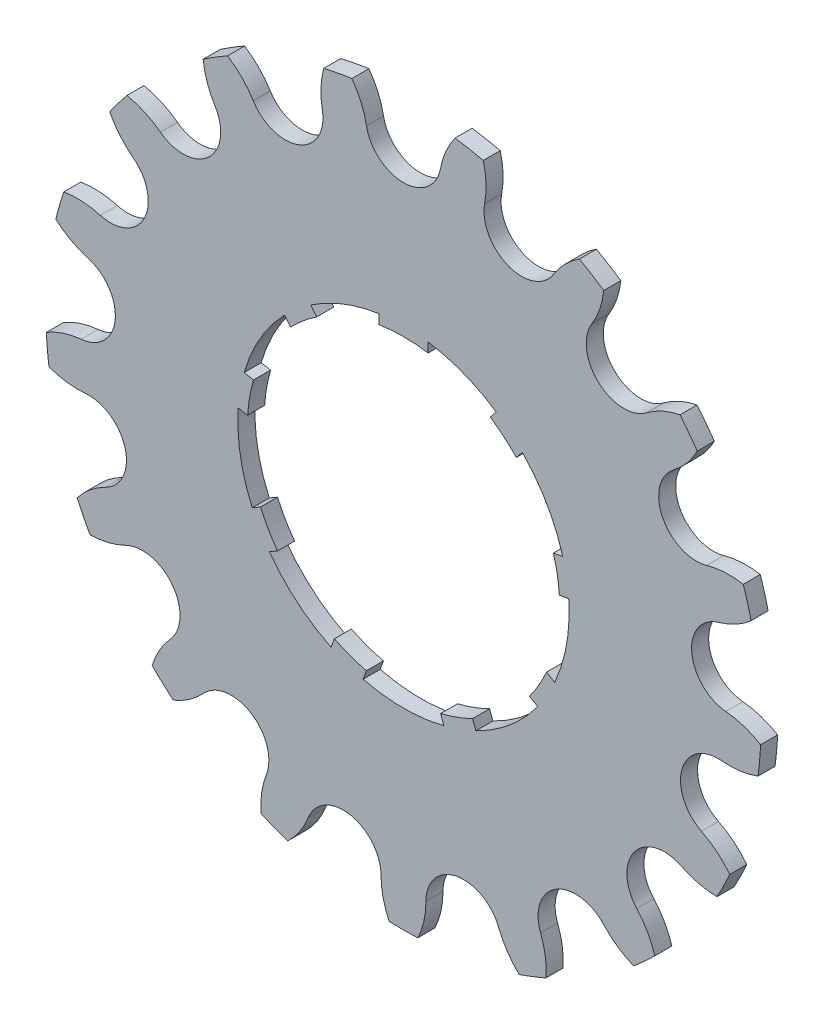
SolidWorks part; units mm, degrees
ref_plane "Alzado" through (0, 0, 0) normal (0, 0, 1) x (1, 0, 0)
ref_plane "Planta" through (0, 0, 0) normal (0, 1, 0) x (1, 0, 0)
ref_plane "Vista lateral" through (0, 0, 0) normal (1, 0, 0) x (0, 0, -1)
sketch "Sk_Disco" plane through (0, 0, 0) normal (0, 0, 1) x (1, 0, 0)
  line L0 (2.6, 17.3058) -> (2.6, 16.2939)
  line L1 (-2.6, 16.2939) -> (-2.6, 17.3058)
  line L2 (-9.8102, 14.4917) -> (-9.1638, 13.7213)
  line L3 (-11.9216, 11.4073) -> (-12.568, 12.1777)
  line L4 (-16.8302, 4.7954) -> (-15.8398, 4.6207)
  line L5 (-16.4649, 1.0754) -> (-17.4553, 1.2501)
  line L6 (-15.9751, -7.1447) -> (-15.1041, -6.6419)
  line L7 (-13.3041, -9.7596) -> (-14.1751, -10.2624)
  line L8 (-7.6451, -15.7418) -> (-7.3011, -14.7968)
  line L9 (-3.9182, -16.028) -> (-4.2622, -16.973)
  line L10 (4.2622, -16.973) -> (3.9182, -16.028)
  line L11 (7.3011, -14.7968) -> (7.6451, -15.7418)
  line L12 (14.1751, -10.2624) -> (13.3041, -9.7596)
  line L13 (15.1041, -6.6419) -> (15.9751, -7.1447)
  line L14 (17.4553, 1.2501) -> (16.4649, 1.0754)
  line L15 (15.8398, 4.6207) -> (16.8302, 4.7954)
  line L16 (12.568, 12.1777) -> (11.9216, 11.4073)
  line L17 (9.1638, 13.7213) -> (9.8102, 14.4917)
  circle A0 centre (0, 0) radius 37.7795
  arc A1 (2.6, 16.2939) -> (-2.6, 16.2939) centre (0, 0) ccw
  arc A2 (-2.6, 17.3058) -> (-9.8102, 14.4917) centre (0, 0) ccw
  arc A3 (-9.1638, 13.7213) -> (-11.9216, 11.4073) centre (0, 0) ccw
  arc A4 (-12.568, 12.1777) -> (-16.8302, 4.7954) centre (0, 0) ccw
  arc A5 (-15.8398, 4.6207) -> (-16.4649, 1.0754) centre (0, 0) ccw
  arc A6 (-17.4553, 1.2501) -> (-15.9751, -7.1447) centre (0, 0) ccw
  arc A7 (-15.1041, -6.6419) -> (-13.3041, -9.7596) centre (0, 0) ccw
  arc A8 (-14.1751, -10.2624) -> (-7.6451, -15.7418) centre (0, 0) ccw
  arc A9 (-7.3011, -14.7968) -> (-3.9182, -16.028) centre (0, 0) ccw
  arc A10 (-4.2622, -16.973) -> (4.2622, -16.973) centre (0, 0) ccw
  arc A11 (3.9182, -16.028) -> (7.3011, -14.7968) centre (0, 0) ccw
  arc A12 (7.6451, -15.7418) -> (14.1751, -10.2624) centre (0, 0) ccw
  arc A13 (13.3041, -9.7596) -> (15.1041, -6.6419) centre (0, 0) ccw
  arc A14 (15.9751, -7.1447) -> (17.4553, 1.2501) centre (0, 0) ccw
  arc A15 (16.4649, 1.0754) -> (15.8398, 4.6207) centre (0, 0) ccw
  arc A16 (16.8302, 4.7954) -> (12.568, 12.1777) centre (0, 0) ccw
  arc A17 (11.9216, 11.4073) -> (9.1638, 13.7213) centre (0, 0) ccw
  arc A18 (9.8102, 14.4917) -> (2.6, 17.3058) centre (0, 0) ccw
  dimension "D1" = 75.559
extrude "Disco" add sketch "Sk_Disco" along normal blind 1.8
sketch "Sk_Hueco" plane through (0, 0, 0) normal (0, 0, 1) x (1, 0, 0)
  line L0 (0, 0) -> (0, 34.5579) construction
  line L1 (0, 0) -> (-12.4838, 32.2243) construction
  line L2 (0, 0) -> (12.4838, 32.2243) construction
  line L3 (0, 34.5579) -> (-12.4838, 32.2243) construction
  line L4 (0, 34.5579) -> (12.4838, 32.2243) construction
  arc A0 (-3.9073, 33.8275) -> (3.9073, 33.8275) centre (0, 34.5579) ccw
  arc A1 (-3.9073, 33.8275) -> (-7.1526, 39.1312) centre (-12.4838, 32.2243) ccw
  arc A2 (7.1526, 39.1312) -> (3.9073, 33.8275) centre (12.4838, 32.2243) ccw
  arc A3 (7.1526, 39.1312) -> (-7.1526, 39.1312) centre (0, 0) ccw
  dimension "D6" = 3.975
  dimension "D7" = 39.7795
  dimension "D1" = 34.5579
  dimension "D2" = 34.5579
  dimension "D3" = 34.5579
  dimension "D4" = 21.176
  dimension "D5" = 21.176
extrude "Hueco_diente" cut sketch "Sk_Hueco" along normal through all
ref_axis "Eje_pinon" through (0, 0, -0.09) along (0, 0, 1)
pattern_circular "Matriz_dientes" count 17 over 360 about axis through (0, 0, -0.09) along (0, 0, 1) of "Hueco_diente"
equation "\"Z\"= 17"
equation "\"p\"= 12.7"
equation "\"Dr\"= 7.75"
equation "\"e\"= 1.8"
equation "\"D\"= \"p\" / sin ( 180 / \"Z\" )"
equation "\"De\"= \"p\" * ( 0.6 + 1 / tan ( 180 / \"Z\" ) )"
equation "\"Di\"= \"D\" - \"Dr\""
equation "\"Ang\"= 360 / \"Z\""
equation "\"D1@Sk_Disco\" = \"De\""
equation "\"D1@Disco\" = \"e\""
equation "\"D1@Sk_Hueco\" = \"D\" / 2"
equation "\"D2@Sk_Hueco\" = \"D\" / 2"
equation "\"D3@Sk_Hueco\" = \"D\" / 2"
equation "\"D4@Sk_Hueco\" = \"Ang\""
equation "\"D5@Sk_Hueco\" = \"Ang\""
equation "\"D6@Sk_Hueco\" = \"Dr\" / 2 + 0.1"
equation "\"D7@Sk_Hueco\" = \"De\" / 2 + 2"
equation "\"D1@Matriz_dientes\" = \"Z\""
